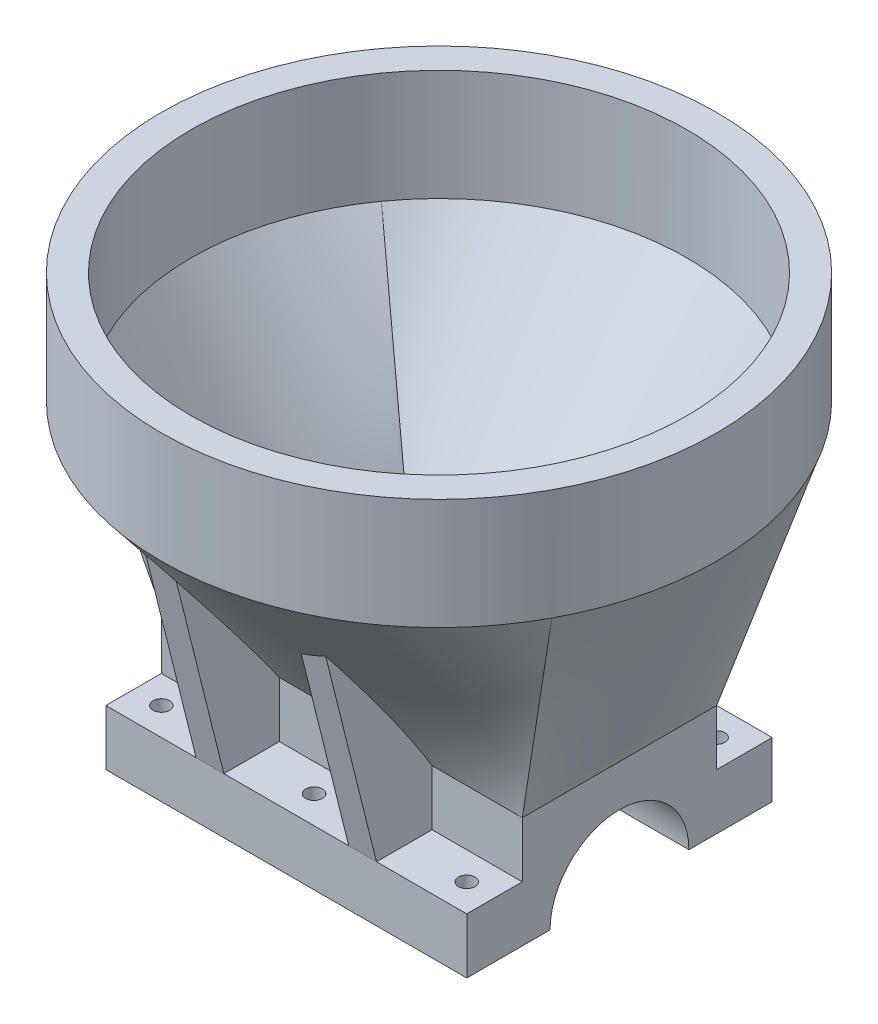
SolidWorks part; units mm, degrees
ref_plane "Alzado" through (0, 0, 0) normal (0, 0, 1) x (1, 0, 0)
ref_plane "Planta" through (0, 0, 0) normal (0, 1, 0) x (1, 0, 0)
ref_plane "Vista lateral" through (0, 0, 0) normal (1, 0, 0) x (0, 0, -1)
sketch "Croquis2" plane through (0, 0, 0) normal (0, 1, 0) x (1, 0, 0)
  line L0 (0, 0) -> (0, 25)
  line L1 (0, 25) -> (35, 25)
  line L2 (35, 25) -> (35, 0)
  line L3 (35, 0) -> (0, 0)
  line L4 (-15, 30) -> (-15, -5)
  line L5 (-15, 30) -> (50, 30)
  line L6 (-15, -5) -> (50, -5)
  line L7 (50, 30) -> (50, -5)
  dimension "D1" = 25
  dimension "D2" = 35
  dimension "D3" = 15
  dimension "D4" = 5
  dimension "D5" = 5
  dimension "D6" = 15
extrude "Saliente-Extruir1" add sketch "Croquis2" along normal blind 20
sketch "Croquis3" plane through (50, 0, 0) normal (1, 0, 0) x (0, 0, -1)
  line L0 (-5, 0) -> (30, 0) construction
  circle A0 centre (12.5, 0) radius 12.5
extrude "Cortar-Extruir1" cut sketch "Croquis3" against normal offset from surface (60 mm away) 5 up to face at (-15, 10, -12.5)
sketch "Croquis4" plane through (-15, 0, 0) normal (-1, 0, 0) x (0, 0, 1)
  line L0 (-30, 0) -> (5, 0) construction
  circle A0 centre (-12.5, 0) radius 6.5
  dimension "D1" = 13
extrude "Cortar-Extruir2" cut sketch "Croquis4" against normal blind 5
sketch "Croquis5" plane through (0, 20, 0) normal (0, 1, 0) x (1, 0, 0)
  line L4 (-15, -5) -> (50, -5) construction
  line L5 (50, -5) -> (50, 30) construction
  line L6 (50, 30) -> (-15, 30) construction
  line L7 (-15, 30) -> (-15, -5) construction
  line L12 (-15, -5) -> (50, -5)
  line L13 (50, -5) -> (50, 30)
  line L14 (50, 30) -> (-15, 30)
  line L15 (-15, 30) -> (-15, -5)
ref_plane "Plano1" through (0, 60, 0) normal (0, 1, 0) x (1, 0, 0)
sketch "Croquis6" plane through (0, 60, 0) normal (0, 1, 0) x (1, 0, 0)
  circle A0 centre (17.5, 12.5) radius 50
  dimension "D1" = 100
sketch "Croquis8" plane through (0, 60, 0) normal (0, 1, 0) x (1, 0, 0)
  circle A0 centre (17.5, 12.5) radius 44.6403
sketch "Croquis9" plane through (0, 20, 0) normal (0, 1, 0) x (1, 0, 0)
  line L1 (0, 0) -> (35, 0)
  line L2 (0, 0) -> (0, 25)
  line L3 (0, 25) -> (35, 25)
  line L4 (35, 0) -> (35, 25)
loft "Recubrir2" add profiles "Croquis5", "Croquis6" connector at (50, 20, -30) connector at (17.5, 60, 37.5)
sketch "Croquis10" plane through (0, 60, 0) normal (0, 1, 0) x (1, 0, 0)
  circle A0 centre (17.5, 12.5) radius 50
  circle A1 centre (17.5, 12.5) radius 44.6403
extrude "Saliente-Extruir2" add sketch "Croquis10" along normal blind 20
sketch "Croquis11" plane through (0, 0, 0) normal (0, -1, 0) x (1, 0, 0)
  line L1 (-15, 5) -> (50, 5)
  line L2 (-15, 5) -> (-15, 15)
  line L3 (-15, 15) -> (50, 15)
  line L4 (50, 5) -> (50, 15)
  line L5 (-15, -30) -> (50, -30)
  line L6 (-15, -30) -> (-15, -40)
  line L7 (-15, -40) -> (50, -40)
  line L8 (50, -30) -> (50, -40)
  circle A0 centre (45, 10) radius 1.5
  circle A1 centre (45, -35) radius 1.5
  circle A2 centre (-10, -35) radius 1.5
  circle A3 centre (-10, 10) radius 1.5
  circle A4 centre (17.5, 10) radius 1.5
  circle A5 centre (17.5, -35) radius 1.5
  dimension "D3" = 3
  dimension "D4" = 3
  dimension "D5" = 3
  dimension "D6" = 3
  dimension "D7" = 3
  dimension "D8" = 3
  dimension "D1" = 10
  dimension "D2" = 10
  dimension "D9" = 5
  dimension "D10" = 5
  dimension "D11" = 5
  dimension "D12" = 5
extrude "Saliente-Extruir3" add sketch "Croquis11" against normal blind 10
ref_plane "Plano2" through (31.25, 0, 0) normal (1, 0, 0) x (0, 0, -1)
sketch "Croquis12" plane through (31.25, 0, 0) normal (1, 0, 0) x (0, 0, -1)
  line L0 (-5, 10) -> (-5, 50)
  line L2 (-5, 50) -> (-25, 50)
  line L4 (-15, 10) -> (-25, 50)
  line L5 (-5, 10) -> (-15, 10)
  line L6 (12.5, 0) -> (12.5, 80) construction
  line L7 (62.5, 80) -> (-37.5, 80) construction
  line L8 (30, 10) -> (40, 10)
  line L9 (40, 10) -> (50.3125, 50)
  line L10 (30, 50) -> (50.3125, 50)
  line L11 (30, 10) -> (30, 50)
  dimension "D1" = 40
  dimension "D2" = 20
extrude "Saliente-Extruir4" add sketch "Croquis12" along normal blind 2.5 and the other way blind 2.5
ref_plane "Plano4" through (17.5, 0, 0) normal (1, 0, 0) x (0, 0, -1)
mirror "Simetría1" about plane through (17.5, 0, 0) normal (1, 0, 0) of "Saliente-Extruir4"
loft "Cortar-Recubrir2" cut profiles "Croquis9", "Croquis8" connector at (0, 20, 0) connector at (17.5, 60, 32.1403)
